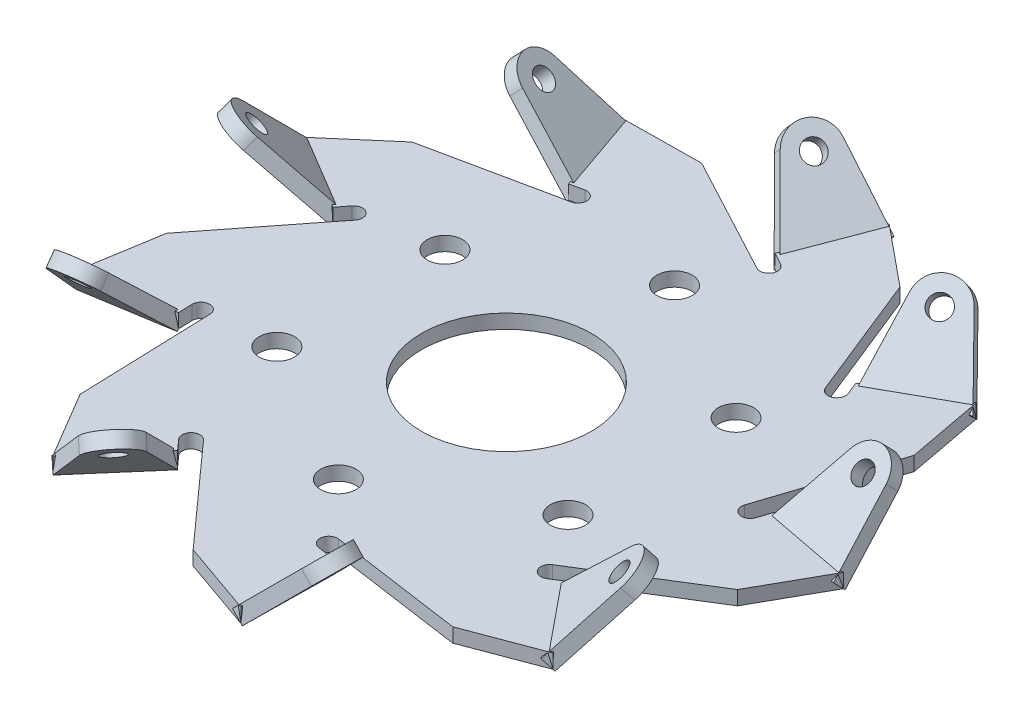
SolidWorks part; units mm, degrees
material "1060 Alloy"
ref_plane "Front Plane" through (0, 0, 0) normal (0, 0, 1) x (1, 0, 0)
ref_plane "Top Plane" through (0, 0, 0) normal (0, 1, 0) x (1, 0, 0)
ref_plane "Right Plane" through (0, 0, 0) normal (1, 0, 0) x (0, 0, -1)
ref_plane "Top" through (0, 46, 0) normal (0, -1, 0) x (-1, 0, 0)
sketch3d "3DSketch2"
  line L0 (8.6824, 0, -49.2404) -> (-26.2317, 0, 42.5664) construction
  line L1 (-47.4558, 0, 15.7464) -> (38.3022, 0, -32.1394) construction
  line L2 (0, 0, 0) -> (0, 46, 0) construction
  line L3 (7.2665, 0, 49.4692) -> (-25, 0, -43.3013) construction
  line L4 (-46.9846, 0, -17.101) -> (37.3646, 0, 33.2247) construction
  line L5 (-46.4748, 0, -18.4416) -> (50, 0, 0) construction
  line L6 (-23.7477, 0, -44.0005) -> (38.3022, 0, 32.1394) construction
  line L7 (10.0912, 0, -48.9711) -> (8.6824, 0, 49.2404) construction
  line L8 (39.2083, 0, -31.0276) -> (-25, 0, 43.3013) construction
  line L9 (49.9794, 0, 1.4341) -> (-46.9846, 0, 17.101) construction
  line L10 (0, 0, 0) -> (50, 0, 0) construction
  line L11 (-49.8989, 46, -3.1773) -> (45.209, 46, 21.3576) construction
  line L12 (0, 46, 0) -> (-2.345, 46, 9.0902) construction
  line L13 (50, 0, 0) -> (-46.4748, 0, -18.4416) construction
  line L14 (50, 0, 0) -> (51.8775, 0, -9.8222) construction
  line L15 (-46.4748, 0, -18.4416) -> (-44.5973, 0, -28.2637) construction
  line L16 (51.8775, 0, -9.8222) -> (-44.5973, 0, -28.2637) construction
  line L17 (51.8775, 0, -9.8222) -> (51.8775, 10, -9.8222) construction
  line L18 (51.8775, 10, -9.8222) -> (50, 0, 0) construction
  line L19 (51.8775, 10, -9.8222) -> (51.8775, 0, -9.8222) construction
  line L20 (51.8775, 10, -9.8222) -> (-44.5973, 10, -28.2637) construction
  line L21 (51.8775, 0, -9.8222) -> (-44.5973, 0, -28.2637) construction
  line L22 (-44.5973, 10, -28.2637) -> (-44.5973, 0, -28.2637) construction
  line L23 (-44.5973, 10, -28.2637) -> (-46.4748, 0, -18.4416) construction
  line L24 (-49.8989, 46, -3.1773) -> (45.209, 46, 21.3576) construction
  line L25 (-49.8989, 46, -3.1773) -> (-52.3969, 46, 6.5057) construction
  line L26 (45.209, 46, 21.3576) -> (42.7111, 46, 31.0406) construction
  line L27 (-52.3969, 46, 6.5057) -> (42.7111, 46, 31.0406) construction
  line L28 (42.7111, 46, 31.0406) -> (42.7111, 36, 31.0406) construction
  line L29 (-52.3969, 46, 6.5057) -> (-52.3969, 36, 6.5057) construction
  line L30 (-52.3969, 36, 6.5057) -> (42.7111, 36, 31.0406) construction
  line L31 (45.209, 46, 21.3576) -> (42.7111, 36, 31.0406) construction
  line L32 (-52.3969, 36, 6.5057) -> (-49.8989, 46, -3.1773) construction
  line L33 (43.7018, 39.9663, 27.2) -> (51.1329, 6.0337, -5.9264) construction
  circle A0 centre (0, 0, 0) radius 9.3877 construction
  circle A1 centre (0, 0, 0) radius 50 construction
  circle A2 centre (0, 46, 0) radius 50 construction
  circle A3 centre (0, 46, 0) radius 9.3877 construction
  point P2 (0, 9.3877, 0)
  point P6 (-8.7746, 0, -3.337)
  point P9 (-4.5768, 0, -8.1965)
  point P12 (0, 50, 0)
  point P30 (0, 96, 0)
  point P32 (0, 36.6123, 0)
  dimension "D1" = 140
  dimension "D2" = 140
  dimension "D3" = 100
  dimension "D6" = 10
  dimension "D12" = 10
  dimension "D4" = 140
  dimension "D5" = 140
  dimension "D7" = 140
  dimension "D8" = 140
  dimension "D9" = 140
  dimension "D10" = 140
  dimension "D11" = 10
  dimension "D13" = 10
  dimension "D14" = 48
ref_plane "Plane3" through (0.8813, -4.6939, -4.6104) normal (-0.1328, 0.7071, 0.6945) x (0.9911, 0.0947, 0.093)
ref_plane "Plane4" through (-6.9177, 27.6939, 26.816) normal (0.1766, -0.7071, -0.6847) x (-0.9843, -0.1269, -0.1229)
ref_plane "Plane5" through (0, 23, 0) normal (0, 1, 0) x (1, 0, 0)
ref_axis "Axis2" through (57.7806, 23, -21.9291) along (-0.9822, 0, -0.1878)
sketch "Sketch3" plane through (0, 23, 0) normal (0, 1, 0) x (1, 0, 0)
  line L0 (-49.1108, 9.3877) -> (49.1108, -9.3877) construction
  line L1 (57.7806, 21.9291) -> (-51.3924, 42.7981) construction
  line L2 (49.1108, -9.3877) -> (29.6629, -5.6702) construction
  circle A0 centre (0, 0) radius 50 construction
  circle A1 centre (0, 0) radius 50 construction
  point P0 (0, 0)
  dimension "D1" = 19.8
sketch3d "3DSketch3"
  line L0 (34.35, 46, 29.9826) -> (44.4237, 0, -14.9246) construction
  line L1 (43.7018, 39.9663, 27.2) -> (51.1329, 6.0337, -5.9264) construction
  line L2 (49.1108, 23, 9.3877) -> (29.6629, 23, 5.6702) construction
  line L3 (35.5615, 40.468, 24.582) -> (42.9332, 6.8061, -8.2802) construction
  line L4 (42.9332, 6.8061, -8.2802) -> (41.6553, 0, -1.5951) construction
  line L5 (50, 0, 0) -> (-46.4748, 0, -18.4416) construction
  line L6 (41.6553, 0, -1.5951) -> (44.4237, 0, -14.9246) construction
  line L7 (41.6553, 0, -1.5951) -> (43.6126, 0, -11.0193) construction
  line L8 (41.6553, 0, -1.5951) -> (42.4693, -3.7167, -5.2236) construction
  point P7 (39.3869, 23, 7.529)
  point P10 (39.3869, 23, 7.529)
sketch "Sketch4" plane through (0, 0, 0) normal (0, 1, 0) x (1, 0, 0)
  line L0 (-34.6713, 40.362) -> (33.7282, 41.1533) construction
  line L1 (-0.6156, 53.2053) -> (-34.6713, 40.362) construction
  line L2 (-34.6713, 40.362) -> (-52.5039, 8.6328) construction
  line L3 (-52.5039, 8.6328) -> (-45.7694, -27.1358) construction
  line L4 (-45.7694, -27.1358) -> (-17.6189, -50.2072) construction
  line L5 (-17.6189, -50.2072) -> (18.7757, -49.7861) construction
  line L6 (18.7757, -49.7861) -> (46.3849, -26.0696) construction
  line L7 (46.3849, -26.0696) -> (52.2901, 9.8452) construction
  line L8 (52.2901, 9.8452) -> (33.7282, 41.1533) construction
  line L9 (33.7282, 41.1533) -> (-0.6156, 53.2053) construction
  line L10 (-0.6156, 53.2053) -> (-52.5039, 8.6328) construction
  line L11 (-52.5039, 8.6328) -> (-17.6189, -50.2072) construction
  line L12 (-17.6189, -50.2072) -> (46.3849, -26.0696) construction
  line L13 (46.3849, -26.0696) -> (33.7282, 41.1533) construction
  line L14 (-0.6156, 53.2053) -> (52.2901, 9.8452) construction
  line L15 (-34.6713, 40.362) -> (-45.7694, -27.1358) construction
  line L16 (-45.7694, -27.1358) -> (18.7757, -49.7861) construction
  line L17 (52.2901, 9.8452) -> (18.7757, -49.7861) construction
  line L19 (-46.4748, 18.4416) -> (50, 0) construction
  line L20 (-47.4558, -15.7464) -> (38.3022, 32.1394) construction
  line L81 (-7.5601, 6.5307) -> (35.699, 30.6858) construction
  line L82 (-1.5935, 9.8623) -> (-7.5601, 6.5307) construction
  line L91 (-1.5935, 9.8623) -> (47.0715, 0.5598) construction
  line L92 (5.1187, 8.5793) -> (36.4187, -29.8281) construction
  line L93 (9.4358, 3.2819) -> (8.7252, -46.2591) construction
  line L94 (9.3378, -3.5512) -> (-23.0509, -41.045) construction
  line L95 (4.8705, -8.7225) -> (-44.0413, -16.6254) construction
  line L96 (-1.8757, -9.8126) -> (-44.4242, 15.5734) construction
  line L97 (-7.7443, -6.3112) -> (-24.0205, 40.4852) construction
  line L98 (-9.9892, 0.1433) -> (7.6226, 46.4536) construction
  line L99 (31.5748, 1.0419) -> (16.1303, 39.4809) construction
  line L100 (4.4568, 31.2761) -> (-16.6897, 26.8237) construction
  line L101 (-16.6897, 26.8237) -> (-30.027, 9.8202) construction
  line L102 (-30.027, 9.8202) -> (-29.3143, -11.7783) construction
  line L103 (-29.3143, -11.7783) -> (-14.8851, -27.8656) construction
  line L104 (-14.8851, -27.8656) -> (6.509, -30.9142) construction
  line L105 (6.509, -30.9142) -> (24.8575, -19.4978) construction
  line L106 (24.8575, -19.4978) -> (31.5748, 1.0419) construction
  line L107 (31.5748, 1.0419) -> (23.518, 21.0941) construction
  line L108 (23.518, 21.0941) -> (4.4568, 31.2761) construction
  line L109 (23.518, 21.0941) -> (-13.0213, 40.6125) construction
  line L110 (4.4568, 31.2761) -> (-36.0801, 22.741) construction
  line L111 (-16.6897, 26.8237) -> (-42.2566, -5.7712) construction
  line L112 (-30.027, 9.8202) -> (-28.6608, -31.583) construction
  line L113 (-29.3143, -11.7783) -> (-1.6543, -42.6168) construction
  line L114 (-14.8851, -27.8656) -> (26.1263, -33.7097) construction
  line L115 (6.509, -30.9142) -> (41.6821, -9.0295) construction
  line L116 (24.8575, -19.4978) -> (37.7343, 19.8757) construction
  line L117 (16.1303, 39.4809) -> (7.6226, 46.4536)
  line L118 (-13.0213, 40.6125) -> (-24.0205, 40.4852)
  line L119 (-36.0801, 22.741) -> (-44.4242, 15.5734)
  line L120 (-42.2566, -5.7712) -> (-44.0413, -16.6254)
  line L121 (-28.6608, -31.583) -> (-23.0509, -41.045)
  line L122 (-1.6543, -42.6168) -> (8.7252, -46.2591)
  line L123 (26.1263, -33.7097) -> (36.4187, -29.8281)
  line L124 (41.6821, -9.0295) -> (47.0715, 0.5598)
  line L125 (37.7343, 19.8757) -> (35.699, 30.6858)
  line L126 (-24.0205, 40.4852) -> (-19.0929, 26.3177)
  line L127 (-44.4242, 15.5734) -> (-31.5427, 7.8878)
  line L128 (-44.0413, -16.6254) -> (-29.2333, -14.2328)
  line L129 (-23.0509, -41.045) -> (-13.2453, -29.6938)
  line L130 (8.7252, -46.2591) -> (8.9403, -31.2607)
  line L131 (36.4187, -29.8281) -> (26.9427, -18.2004)
  line L132 (47.0715, 0.5598) -> (32.3382, 3.3761)
  line L133 (35.699, 30.6858) -> (22.6024, 23.3729)
  line L134 (7.6226, 46.4536) -> (2.2906, 32.4332)
  line L135 (-13.0213, 40.6125) -> (2.2906, 32.4332)
  line L136 (16.1303, 39.4809) -> (22.6024, 23.3729)
  line L137 (37.7343, 19.8757) -> (32.3382, 3.3761)
  line L138 (41.6821, -9.0295) -> (26.9427, -18.2004)
  line L139 (26.1263, -33.7097) -> (8.9403, -31.2607)
  line L140 (-1.6543, -42.6168) -> (-13.2453, -29.6938)
  line L141 (-28.6608, -31.583) -> (-29.2333, -14.2328)
  line L142 (-42.2566, -5.7712) -> (-31.5427, 7.8878)
  line L143 (-36.0801, 22.741) -> (-19.0929, 26.3177)
  circle A0 centre (0, 0) radius 50 construction
  circle A6 centre (0, 0) radius 9.9902 construction
  circle A7 centre (0, 0) radius 29.6868 construction
  point P28 (0, 0)
  point P91 (0, 0)
  dimension "D1" = 100
  dimension "D2" = 11
  dimension "D3" = 15
sketch "Sketch5" plane through (0, 0, 0) normal (0, 1, 0) x (1, 0, 0)
  line L0 (24.7852, 24.5917) -> (35.699, 30.6858)
  line L1 (35.699, 30.6858) -> (37.7343, 19.8757)
  line L2 (37.7343, 19.8757) -> (32.3382, 3.3761)
  line L3 (34.7938, 2.9067) -> (47.0715, 0.5598)
  line L4 (47.0715, 0.5598) -> (41.6821, -9.0295)
  line L5 (41.6821, -9.0295) -> (26.9427, -18.2004)
  line L6 (28.522, -20.1383) -> (36.4187, -29.8281)
  line L7 (36.4187, -29.8281) -> (26.1263, -33.7097)
  line L8 (26.1263, -33.7097) -> (8.9403, -31.2607)
  line L9 (8.9045, -33.7604) -> (8.7252, -46.2591)
  line L10 (8.7252, -46.2591) -> (-1.6543, -42.6168)
  line L11 (-1.6543, -42.6168) -> (-13.2453, -29.6938)
  line L12 (-14.8796, -31.5857) -> (-23.0509, -41.045)
  line L13 (-23.0509, -41.045) -> (-28.6608, -31.583)
  line L14 (-28.6608, -31.583) -> (-29.2333, -14.2328)
  line L15 (-31.7013, -14.6316) -> (-44.0413, -16.6254)
  line L16 (-44.0413, -16.6254) -> (-42.2566, -5.7712)
  line L17 (-42.2566, -5.7712) -> (-31.5427, 7.8878)
  line L18 (-33.6896, 9.1687) -> (-44.4242, 15.5734)
  line L19 (-44.4242, 15.5734) -> (-36.0801, 22.741)
  line L20 (-36.0801, 22.741) -> (-19.0929, 26.3177)
  line L21 (-19.9142, 28.6789) -> (-24.0205, 40.4852)
  line L22 (-24.0205, 40.4852) -> (-13.0213, 40.6125)
  line L23 (-13.0213, 40.6125) -> (2.2906, 32.4332)
  line L24 (3.1793, 34.7699) -> (7.6226, 46.4536)
  line L25 (7.6226, 46.4536) -> (16.1303, 39.4809)
  line L26 (16.1303, 39.4809) -> (22.6024, 23.3729)
  line L27 (-1.5935, 9.8623) -> (47.0715, 0.5598) construction
  line L28 (0, 23.75) -> (-20.5681, 11.875) construction
  line L29 (-20.5681, 11.875) -> (-20.5681, -11.875) construction
  line L30 (-20.5681, -11.875) -> (0, -23.75) construction
  line L31 (0, -23.75) -> (20.5681, -11.875) construction
  line L32 (20.5681, -11.875) -> (20.5681, 11.875) construction
  line L33 (20.5681, 11.875) -> (0, 23.75) construction
  line L34 (24.8575, -19.4978) -> (37.7343, 19.8757) construction
  line L35 (33.0113, 1.4453) -> (32.6259, 0.2668) construction
  line L36 (24.8575, -19.4978) -> (31.5748, 1.0419) construction
  line L37 (34.7938, 2.9067) -> (34.1898, 1.0599)
  line L38 (47.0715, 0.5598) -> (32.3382, 3.3761) construction
  line L39 (32.3382, 3.3761) -> (31.8328, 1.8307)
  line L40 (28.522, -20.1383) -> (26.8722, -21.1648)
  line L41 (26.9427, -18.2004) -> (25.5621, -19.0593)
  line L42 (8.9045, -33.7604) -> (6.9808, -33.4863)
  line L43 (8.9403, -31.2607) -> (7.3306, -31.0313)
  line L44 (-14.8796, -31.5857) -> (-16.177, -30.1392)
  line L45 (-13.2453, -29.6938) -> (-14.331, -28.4834)
  line L46 (-31.7013, -14.6316) -> (-31.7654, -12.6896)
  line L47 (-29.2333, -14.2328) -> (-29.2869, -12.6078)
  line L48 (-33.6896, 9.1687) -> (-32.4904, 10.6976)
  line L49 (-31.5427, 7.8878) -> (-30.5392, 9.1672)
  line L50 (-19.9142, 28.6789) -> (-18.0128, 29.0793)
  line L51 (-19.0929, 26.3177) -> (-17.5019, 26.6527)
  line L52 (3.1793, 34.7699) -> (4.8932, 33.8544)
  line L53 (2.2906, 32.4332) -> (3.7248, 31.6671)
  line L54 (24.7852, 24.5917) -> (25.5096, 22.7887)
  line L55 (22.6024, 23.3729) -> (23.2086, 21.8641)
  line L56 (20.5681, 11.875) -> (20.5681, 0) construction
  line L57 (0, 0) -> (50, 0) construction
  circle A0 centre (0, 0) radius 23.75 construction
  circle A1 centre (20.5681, 11.875) radius 2.5 construction
  circle A2 centre (20.5681, -11.875) radius 2.5 construction
  circle A3 centre (0, -23.75) radius 2.5 construction
  circle A4 centre (-20.5681, -11.875) radius 2.5 construction
  circle A5 centre (-20.5681, 11.875) radius 2.5 construction
  circle A6 centre (0, 23.75) radius 2.5 construction
  arc A7 (31.8328, 1.8307) -> (34.1898, 1.0599) centre (33.0113, 1.4453) ccw
  arc A8 (25.5621, -19.0593) -> (26.8722, -21.1648) centre (26.2171, -20.1121) ccw
  arc A9 (7.3306, -31.0313) -> (6.9808, -33.4863) centre (7.1557, -32.2588) ccw
  arc A10 (-14.331, -28.4834) -> (-16.177, -30.1392) centre (-15.254, -29.3113) ccw
  arc A11 (-29.2869, -12.6078) -> (-31.7654, -12.6896) centre (-30.5262, -12.6487) ccw
  arc A12 (-30.5392, 9.1672) -> (-32.4904, 10.6976) centre (-31.5148, 9.9324) ccw
  arc A13 (-17.5019, 26.6527) -> (-18.0128, 29.0793) centre (-17.7573, 27.866) ccw
  arc A14 (3.7248, 31.6671) -> (4.8932, 33.8544) centre (4.309, 32.7608) ccw
  arc A15 (23.2086, 21.8641) -> (25.5096, 22.7887) centre (24.3591, 22.3264) ccw
  point P78 (0, 0)
  point P131 (0, 0)
  dimension "D1" = 47.5
  dimension "D2" = 5
  dimension "D4" = 2.5
  dimension "D5" = 3
  dimension "D3" = 6
  dimension "D6" = 9
extrude "Boss-Extrude1" add sketch "Sketch5" along normal mid plane 2
sketch "Sketch8" plane through (0, 1, 0) normal (0, 1, 0) x (-1, 0, 0)
  circle A0 centre (0, 23.75) radius 2.5 construction
  circle A1 centre (0, 23.75) radius 2.5
  circle A2 centre (-20.5681, 11.875) radius 2.5
  circle A3 centre (-20.5681, -11.875) radius 2.5
  circle A4 centre (0, 23.75) radius 2.5
  circle A5 centre (20.5681, 11.875) radius 2.5
  circle A6 centre (20.5681, -11.875) radius 2.5
  circle A7 centre (0, -23.75) radius 2.5
extrude "Cut-Extrude1" cut sketch "Sketch8" against normal through all contours A1 | A5 | A2 | A3 | A7 | A6 region at (0, 1, 23.75) region at (20.5681, 1, 11.875) region at (20.5681, 1, -11.875) region at (-20.5681, 1, 11.875) region at (-20.5681, 1, -11.875) region at (0, 1, -23.75)
sketch "Sketch9" plane through (0, 1, 0) normal (0, 1, 0) x (-1, 0, 0)
  circle A0 centre (0, 0) radius 12
  dimension "D1" = 24
extrude "Cut-Extrude2" cut sketch "Sketch9" against normal through all
sketch "Sketch10" plane through (0.8813, -4.6939, -4.6104) normal (-0.1328, 0.7071, 0.6945) x (0.9911, 0.0947, 0.093)
  line L0 (46.508, -0.3014) -> (34.1206, 1.373)
  line L1 (46.508, -0.3014) -> (45.9227, 10.8599)
  line L2 (34.1206, 1.373) -> (39.2675, 12.1813)
  circle A0 centre (42.4275, 10.6766) radius 1.5
  arc A1 (45.9227, 10.8599) -> (39.2675, 12.1813) centre (42.4275, 10.6766) ccw
  dimension "D1" = 3
  dimension "D2" = 2
sketch "Sketch11" plane through (0.8813, -4.6939, -4.6104) normal (-0.1328, 0.7071, 0.6945) x (0.9911, 0.0947, 0.093)
  line L0 (46.508, -0.3014) -> (34.1206, 1.373)
  line L1 (34.1206, 1.373) -> (39.2675, 12.1813)
  line L2 (45.9227, 10.8599) -> (46.508, -0.3014)
  arc A0 (39.2675, 12.1813) -> (45.9227, 10.8599) centre (42.4275, 10.6766) cw
  circle A1 centre (42.4275, 10.6766) radius 1.5
extrude "Boss-Extrude2" add sketch "Sketch11" along normal mid plane 2
pattern_circular "CirPattern1" count 9 over 360 about axis through (0, 0, 0) along (0, 1, 0) of "Boss-Extrude2"
